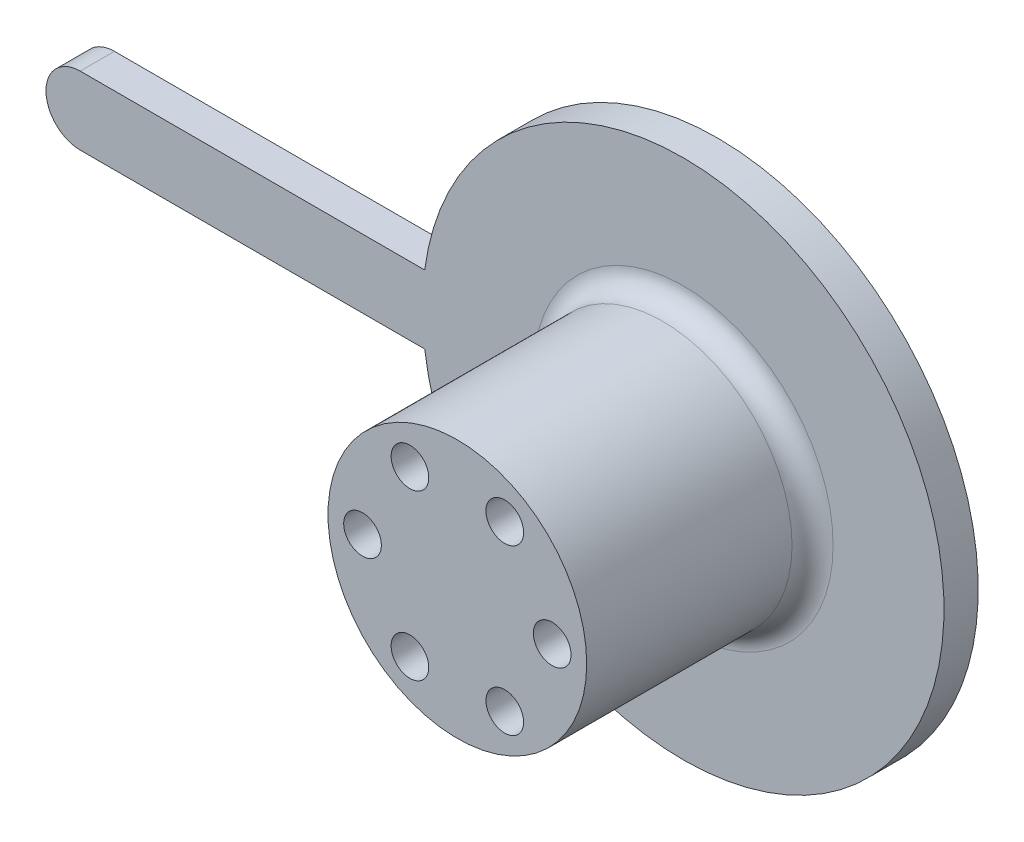
SolidWorks part; units mm, degrees
ref_plane "Front Plane" through (0, 0, 0) normal (0, 0, 1) x (1, 0, 0)
ref_plane "Top Plane" through (0, 0, 0) normal (0, 1, 0) x (1, 0, 0)
ref_plane "Right Plane" through (0, 0, 0) normal (1, 0, 0) x (0, 0, -1)
sketch "Sketch4" plane through (0, 0, 0) normal (0, 0, 1) x (1, 0, 0)
  line L0 (-38.1, 0) -> (-88.1, 0)
  line L1 (-88.1, 0) -> (-88.1, 5)
  line L2 (-88.1, 0) -> (-88.1, -5)
  line L3 (-88.1, 5) -> (-37.7705, 5)
  line L4 (-88.1, -5) -> (-37.7705, -5)
  circle A0 centre (0, 0) radius 38.1
  arc A1 (-88.1, 5) -> (-88.1, -5) centre (-88.1, 0) ccw
  dimension "D1" = 50
  dimension "D2" = 76.2
extrude "Boss-Extrude3" add sketch "Sketch4" along normal blind 5 contours A0 | A0 L3 L1 L0 | A0 L0 L2 L4 | L1 A1 L2 region at (-63.0451, -2.5027, 0) region at (-63.0451, 2.5027, 0) region at (0, 0, 0) region at (-90.2221, 0, 0)
sketch "Sketch5" plane through (0, 0, 5) normal (0, 0, 1) x (1, 0, 0)
  circle A0 centre (0, 0) radius 18.9
extrude "Boss-Extrude4" add sketch "Sketch5" along normal blind 33
fillet "Fillet4" radius 3 1 edges at (18.9, 0, 5)
sketch "Sketch6" plane through (0, 0, 38) normal (0, 0, 1) x (1, 0, 0)
  line L7 (-13.8564, 0) -> (-6.9282, -12)
  line L8 (-6.9282, -12) -> (6.9282, -12)
  line L9 (6.9282, -12) -> (13.8564, 0)
  line L10 (13.8564, 0) -> (6.9282, 12)
  line L11 (6.9282, 12) -> (-6.9282, 12)
  line L12 (-6.9282, 12) -> (-13.8564, 0)
  circle A0 centre (0, 0) radius 12 construction
  circle A7 centre (-13.8564, 0) radius 2.75
  circle A8 centre (-6.9282, 12) radius 2.75
  circle A9 centre (6.9282, 12) radius 2.75
  circle A10 centre (13.8564, 0) radius 2.75
  circle A11 centre (6.9282, -12) radius 2.75
  circle A12 centre (-6.9282, -12) radius 2.75
extrude "Cut-Extrude4" cut sketch "Sketch6" against normal blind 39.48 contours L12 A7 L7 | L7 A7 L12 | L11 A8 L12 | L12 A8 L11 | L10 A9 L11 | L11 A9 L10 | L7 A12 L8 | L8 A12 L7 | L9 A11 L8 | L8 A11 L9 | L9 A10 L10 | L10 A10 L9 region at (-12.3403, 0, 38) region at (-14.6145, 0, 38) region at (-6.1701, -10.687, 38) region at (-7.3072, -12.6565, 38) region at (-7.3072, 12.6565, 38) region at (-6.1701, 10.687, 38) region at (6.1701, -10.687, 38) region at (7.3072, -12.6565, 38) region at (7.3072, 12.6565, 38) region at (6.1701, 10.687, 38) region at (12.3403, 0, 38) region at (14.6145, 0, 38)
